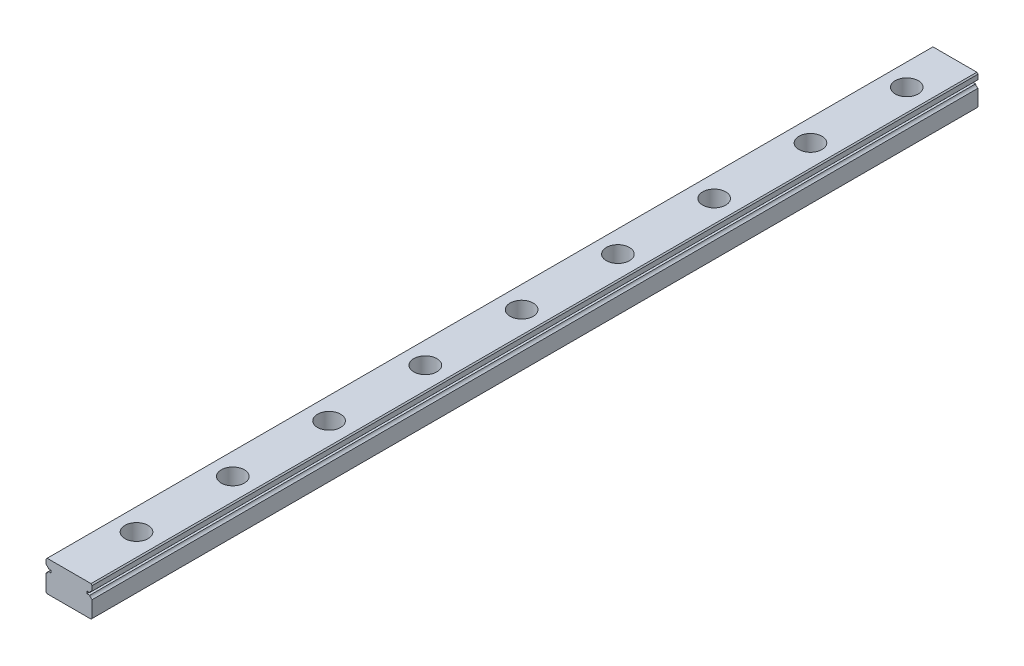
SolidWorks part; units mm, degrees
ref_plane "Спереди" through (0, 0, 0) normal (0, 0, 1) x (1, 0, 0)
ref_plane "Сверху" through (0, 0, 0) normal (0, 1, 0) x (1, 0, 0)
ref_plane "Справа" through (0, 0, 0) normal (1, 0, 0) x (0, 0, -1)
sketch "Эскиз1" plane through (0, 0, 0) normal (0, 0, 1) x (1, 0, 0)
  line L0 (-6, 3.7) -> (-5.7, 4)
  line L1 (-5.7, -4) -> (5.7, -4)
  line L2 (-6, -3.7) -> (-6, 0.549)
  line L3 (-5.7, 4) -> (5.7, 4)
  line L4 (6, -3.7) -> (6, 0.549)
  line L5 (-6, -4) -> (6, 4) construction
  line L6 (-6, 4) -> (6, -4) construction
  line L7 (-6, -3.7) -> (-5.7, -4)
  line L8 (5.7, -4) -> (6, -3.7)
  line L9 (5.7, 4) -> (6, 3.7)
  line L10 (-6, 2.451) -> (-6, 3.7)
  line L11 (-5.3546, 1.7981) -> (-4.6435, 1.7981)
  line L12 (0, 5.4188) -> (0, -5.747) construction
  line L13 (-5.3546, 1.2019) -> (-4.6435, 1.2019)
  line L14 (-4.6435, 1.7981) -> (-4.6435, 1.2019)
  line L15 (4.6435, 1.7981) -> (4.6435, 1.2019)
  line L16 (5.3546, 1.2019) -> (4.6435, 1.2019)
  line L17 (5.3546, 1.7981) -> (4.6435, 1.7981)
  line L18 (6, 2.451) -> (6, 3.7)
  line L19 (4.6435, 1.7981) -> (5.3546, 1.7981) construction
  arc A0 (-6, 0.549) -> (-5.3546, 1.2019) centre (-6.3091, 1.5) ccw
  arc A1 (-5.3546, 1.7981) -> (-6, 2.451) centre (-6.3091, 1.5) ccw
  arc A2 (5.3546, 1.7981) -> (6, 2.451) centre (6.3091, 1.5) cw
  arc A3 (6, 0.549) -> (5.3546, 1.2019) centre (6.3091, 1.5) cw
  point P0 (0, 0)
extrude "Бобышка-Вытянуть1" add sketch "Эскиз1" along normal blind 230
sketch "Эскиз2" plane through (0, 4, 0) normal (0, 1, 0) x (1, 0, 0)
  line L0 (0, 0) -> (0, -26.2396) construction
  line L1 (5.7, 0) -> (-5.7, 0) construction
  line L2 (-3.8306, -12.5) -> (3.8306, -12.5) construction
  circle A0 centre (0, -12.5) radius 3
  circle A1 centre (0, -12.5) radius 1.75
  dimension "D2" = 3.5
  dimension "D3" = 6
  dimension "D1" = 12.5
extrude "Вырез-Вытянуть1" cut sketch "Эскиз2" against normal blind 4.5
extrude "Вырез-Вытянуть2" cut sketch "Эскиз2<2>" against normal through all contours A1 region at (0, 4, 12.5)
sketch "Эскиз2<2>" plane through (0, 4, 0) normal (0, 1, 0) x (1, 0, 0) same geometry as "Эскиз2"
pattern_linear "Линейный массив1" count 10 spacing 25 along (0, 0, 1) of "Вырез-Вытянуть1", "Вырез-Вытянуть2"
